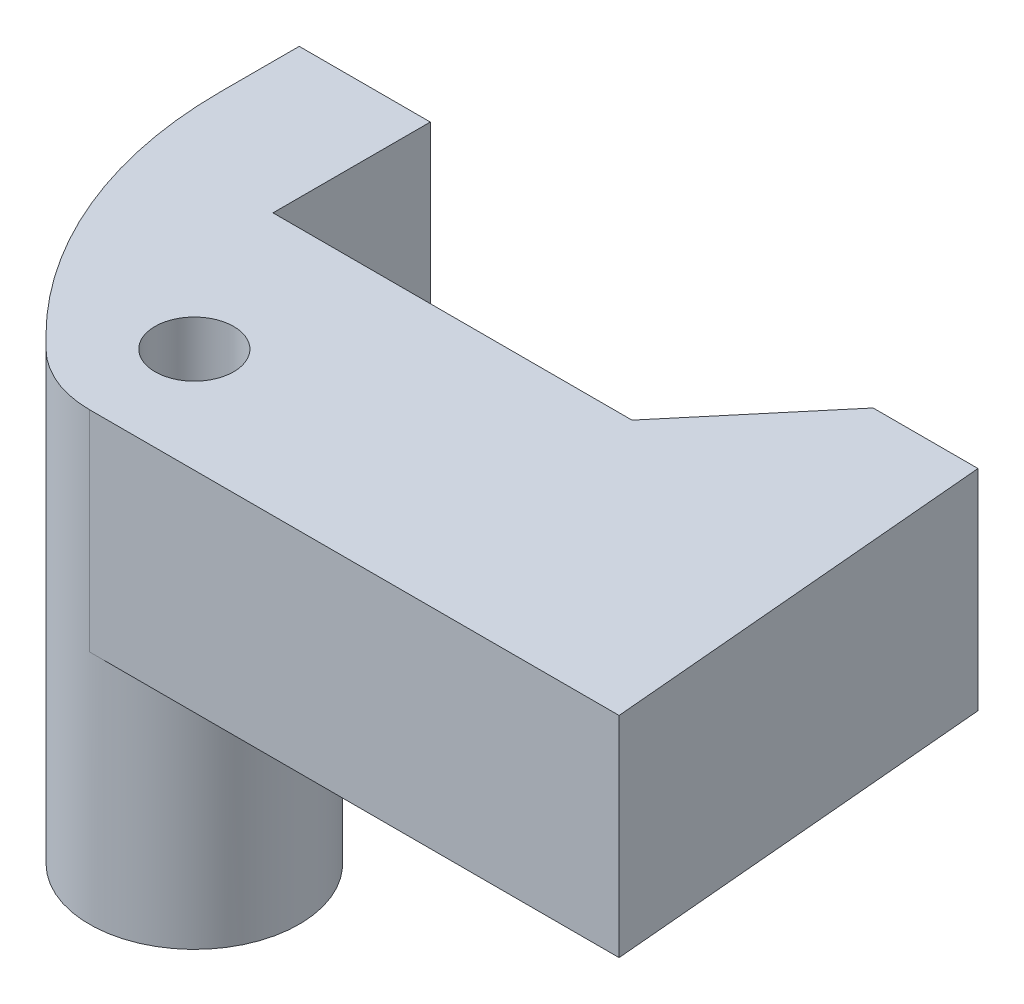
SolidWorks part; units mm, degrees
ref_plane "Front Plane" through (0, 0, 0) normal (0, 0, 1) x (1, 0, 0)
ref_plane "Top Plane" through (0, 0, 0) normal (0, 1, 0) x (1, 0, 0)
ref_plane "Right Plane" through (0, 0, 0) normal (1, 0, 0) x (0, 0, -1)
sketch "Sketch1" plane through (0, 0, 0) normal (0, 1, 0) x (1, 0, 0)
  line L0 (0, 32.3882) -> (0, 7) construction
  line L1 (0, 7) -> (6, 7) construction
  line L2 (6, 7) -> (39, 22.3882) construction
  line L3 (39, 22.3882) -> (72, 7) construction
  line L4 (72, 7) -> (78, 7) construction
  line L5 (78, 7) -> (78, 32.3882) construction
  line L6 (78, 32.3882) -> (0, 32.3882) construction
  line L7 (-11, 13) -> (-11, 16)
  line L8 (11.8877, 15) -> (15.8877, 15)
  line L9 (-3, 0) -> (17.2, 0)
  line L10 (17.5, 15.9916) -> (17.5, 0.8497) construction
  line L11 (17.2, 0) -> (15.8877, 15)
  line L12 (11.8877, 15) -> (7.6922, 10)
  line L13 (7.6922, 10) -> (-6, 10)
  line L14 (-11, 16) -> (-6, 16)
  line L15 (-6, 16) -> (-6, 10)
  line L16 (-5.8284, 1.1716) -> (-6.2929, 1.636)
  line L19 (-3, 4) -> (-3, 0) construction
  circle A0 centre (-3, 4) radius 1.5
  circle A1 centre (-3, 4) radius 4 construction
  circle A2 centre (39, -0.5) radius 21 construction
  circle A3 centre (18.4662, -10) radius 21 construction
  arc A4 (-11, 13) -> (-6.2929, 1.636) centre (5.0711, 13) ccw
  arc A5 (-3, 0) -> (-5.8284, 1.1716) centre (-3, 4) cw
  dimension "D5" = 3
  dimension "D11" = 3
  dimension "D13" = 42
  dimension "D3" = 130
  dimension "D23" = 4
  dimension "D24" = 8
  dimension "D1" = 6
  dimension "D2" = 78
  dimension "D4" = 10
  dimension "D6" = 7
  dimension "D7" = 3
  dimension "D8" = 85
  dimension "D9" = 20.2
  dimension "D10" = 17.5
  dimension "D12" = 15
  dimension "D14" = 4
  dimension "D15" = 3
  dimension "D16" = 50
  dimension "D17" = 4
  dimension "D18" = 10
  dimension "D19" = 0.5
  dimension "D20" = 6
  dimension "D21" = 5
  dimension "D25" = 10
  dimension "D26" = 135
extrude "Boss-Extrude1" add sketch "Sketch1" along normal blind 8
sketch "Sketch2" plane through (0, 0, 0) normal (0, -1, 0) x (1, 0, 0)
  line L0 (-5.8284, -1.1716) -> (-6.2929, -1.636)
  line L3 (-11, -13) -> (-11, -16)
  line L4 (-11, -16) -> (-6, -16)
  line L5 (-6, -16) -> (-6, -8)
  line L6 (-6, -8) -> (-3, -8)
  line L7 (-11, -16) -> (-11, -13) construction
  arc A0 (-3, 0) -> (-3, -8) centre (-3, -4) cw
  circle A1 centre (-3, -4) radius 1.5
  arc A2 (-3, 0) -> (-5.8284, -1.1716) centre (-3, -4) ccw
  arc A3 (-6.2929, -1.636) -> (-11, -13) centre (5.0711, -13) ccw construction
  arc A4 (-6.2929, -1.636) -> (-11, -13) centre (5.0711, -13) ccw
  dimension "D2" = 3
extrude "Boss-Extrude2" add sketch "Sketch2" along normal blind 9
